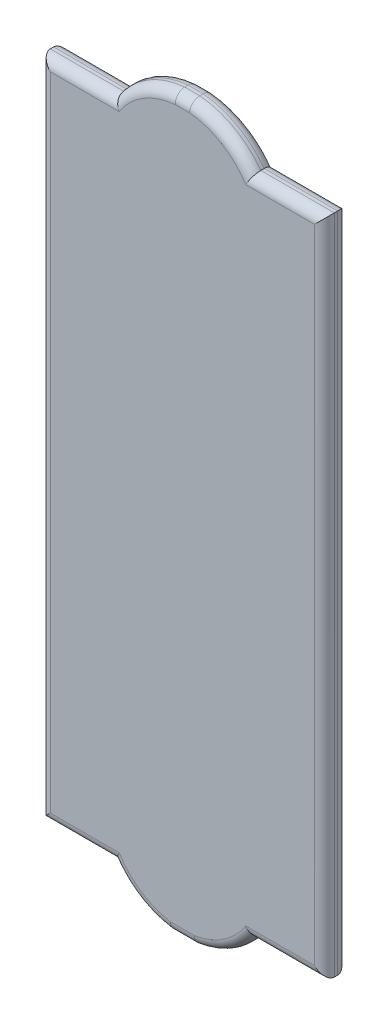
SolidWorks part; units mm, degrees
ref_plane "Plano frontal" through (0, 0, 0) normal (0, 0, 1) x (1, 0, 0)
ref_plane "Plano superior" through (0, 0, 0) normal (0, 1, 0) x (1, 0, 0)
ref_plane "Plano direito" through (0, 0, 0) normal (1, 0, 0) x (0, 0, -1)
sketch "Esboço1" plane through (0, 0, 0) normal (1, 0, 0) x (0, 0, -1)
  line L1 (-2.14, -5.5) -> (2.14, -5.5)
  line L2 (-2.14, -5.5) -> (-2.14, 5.5)
  line L3 (-2.14, 5.5) -> (2.14, 5.5)
  line L4 (2.14, -5.5) -> (2.14, 5.5)
  line L5 (-2.14, -5.5) -> (2.14, 5.5) construction
  line L6 (-2.14, 5.5) -> (2.14, -5.5) construction
  point P0 (0, 0)
  dimension "D1" = 11
  dimension "D2" = 4.28
extrude "Ressalto-extrusão1" add sketch "Esboço1" along normal blind 11
sketch "Esboço4" plane through (0, 0, -2.14) normal (0, 0, -1) x (-1, 0, 0)
  line L0 (-11, -5.5) -> (0, -5.5) construction
  line L4 (-6.72, 5.5) -> (-6.72, -5.5)
  line L5 (-6.72, 5.5) -> (-6.4793, 6.7862)
  line L6 (-6.4793, 6.7862) -> (2.2655, 6.3113)
  line L7 (2.2655, 6.3113) -> (2.2655, -6.9247)
  line L8 (2.2655, -6.9247) -> (-6.72, -6.9247)
  line L9 (-6.72, -6.9247) -> (-6.72, -5.5)
extrude "Corte-extrusão1" cut sketch "Esboço4" against normal blind 8.18 and the other way blind 14
sketch "Esboço5" plane through (0, -5.5, 0) normal (0, -1, 0) x (1, 0, 0)
  line L0 (6.0194, -1.79) -> (11.6174, -1.79)
  line L1 (11, -2.14) -> (6.72, -2.14) construction
  line L2 (6.0194, -1.79) -> (6.0194, -1.4873)
  line L3 (6.1857, 3.0761) -> (11.9962, 3.0761)
  line L4 (11.9962, 3.0761) -> (11.6174, -1.79)
  line L5 (6.0194, -1.4873) -> (6.0194, -1.3764)
  line L6 (6.1857, 3.0761) -> (6.0194, -1.3764)
  dimension "D1" = 0.35
extrude "Corte-extrusão3" cut sketch "Esboço5" against normal blind 12.18 and the other way blind 13
sketch "Esboço6" plane through (0, 0, -2.14) normal (0, 0, -1) x (-1, 0, 0)
  line L0 (-11, 5.5) -> (-6.72, 5.5) construction
  line L2 (-7.8272, 4.9858) -> (-6.3552, 4.9858)
  line L3 (-11.3648, 4.9858) -> (-11.1257, 7.451)
  line L4 (-11.1257, 7.451) -> (-5.9401, 7.451)
  line L5 (-8.8604, 5.5051) -> (-8.86, 5.5) construction
  line L6 (-8.86, 5.5) -> (-8.8596, 5.5051) construction
  line L7 (-7.8272, -4.9858) -> (-6.3552, -4.9858)
  line L8 (-11.3648, -4.9858) -> (-9.8928, -4.9858)
  line L10 (-11.3648, 4.9858) -> (-9.8928, 4.9858)
  line L12 (-5.9401, 7.451) -> (-6.3552, 4.9858)
  line L13 (-6.3552, -4.9858) -> (-6.5458, -6.9507)
  line L14 (-6.5458, -6.9507) -> (-10.1829, -6.9507)
  line L15 (-10.1829, -6.9507) -> (-13.1757, -6.6606)
  line L16 (-13.1757, -6.6606) -> (-11.3648, -4.9858)
  arc A0 (-9.8928, 4.9858) -> (-7.8272, 4.9858) centre (-8.86, 4.2184) cw
  arc A1 (-9.8928, -4.9858) -> (-7.8272, -4.9858) centre (-8.86, -4.2411) ccw
  point P0 (-8.86, 5.5)
  point P7 (-8.86, 0)
extrude "Corte-extrusão5" cut sketch "Esboço6" along normal blind 7.18 and the other way blind 13
fillet "Filete2" radius 0.15 24 edges at (9.5234, -5.3278, -1.79) (8.86, -5.5, -1.79) (8.1966, -5.3278, -1.79) (7.2736, -4.9858, -1.79) (6.72, 0, -1.79) (7.2736, 4.9858, -1.79) (8.2316, 5.3412, -1.79) (8.86, 5.5, -1.79) (9.4884, 5.3412, -1.79) (10.4464, 4.9858, -1.79) (11, 0, -1.79) (10.4464, -4.9858, -1.79) (10.4464, 4.9858, -2.14) (9.4884, 5.3412, -2.14) (8.86, 5.5, -2.14) (8.2316, 5.3412, -2.14) (7.2736, 4.9858, -2.14) (6.72, 0, -2.14) (7.2736, -4.9858, -2.14) (8.1966, -5.3278, -2.14) (8.86, -5.5, -2.14) (9.5234, -5.3278, -2.14) (10.4464, -4.9858, -2.14) (11, 0, -2.14)
